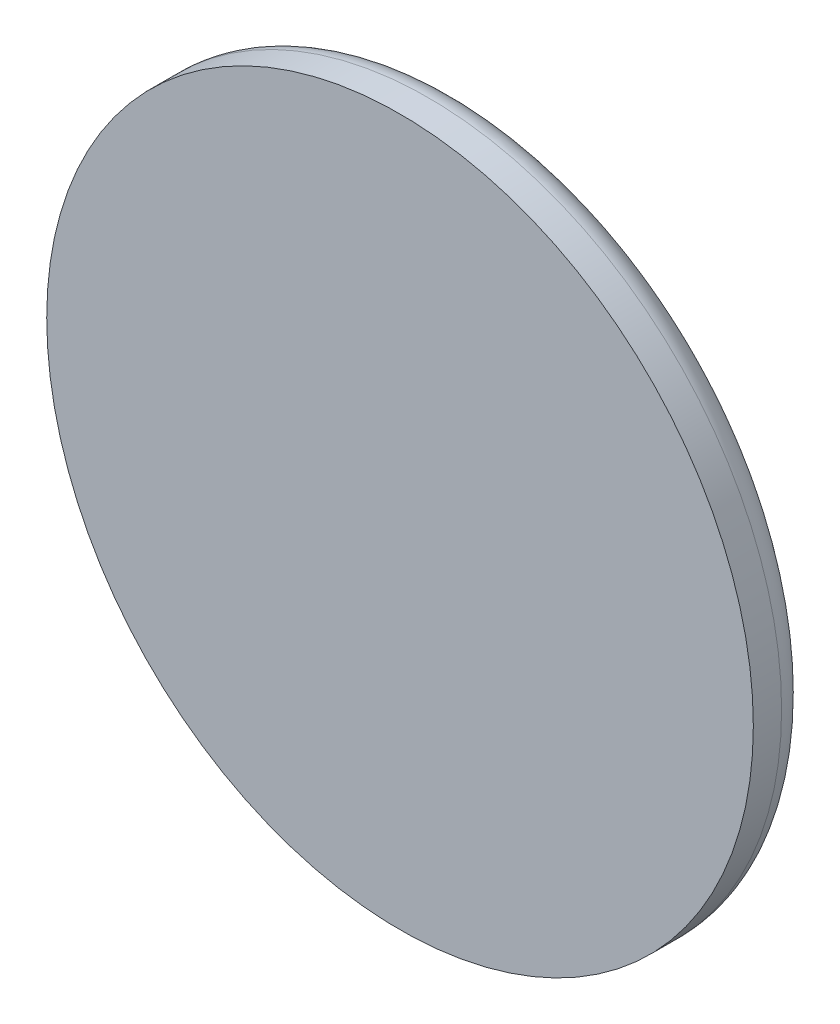
SolidWorks part; units mm, degrees
ref_plane "Front Plane" through (0, 0, 0) normal (0, 0, 1) x (1, 0, 0)
ref_plane "Top Plane" through (0, 0, 0) normal (0, 1, 0) x (1, 0, 0)
ref_plane "Right Plane" through (0, 0, 0) normal (1, 0, 0) x (0, 0, -1)
sketch "Base_Sketch" plane through (0, 0, 0) normal (0, 0, 1) x (1, 0, 0)
  circle A0 centre (0, 0) radius 62.5
  circle A1 centre (0, 0) radius 10
  circle A2 centre (0, 0) radius 5
  dimension "D2" = 10
  dimension "D3" = 125
  dimension "D1" = 5
extrude "Boss-Extrude1" add sketch "Base_Sketch" against normal blind 10 contours A0 A1 | A1 region at (-60.7322, 0, 0)
extrude "Boss-Extrude2" add sketch "Base_Sketch<3>" against normal blind 25 from surface contours A1 A2 region at (-9.7172, 0, 0) starting at face at (62.5, 0, -10)
sketch "Base_Sketch<3>" plane through (0, 0, 0) normal (0, 0, 1) x (1, 0, 0) same geometry as "Base_Sketch"
fillet "Fillet1" radius 5 2 edges at (62.5, 0, -10) (10, 0, -10)
chamfer "Chamfer1" distance 2 angle 45 1 edges at (10, 0, -35)
sketch "Screw_Hole_Ref" plane through (0, 0, -35) normal (0, 0, -1) x (-1, 0, 0)
  line L0 (0, 0) -> (0, 10)
  line L1 (0, 10) -> (-14.3302, 10) construction
  line L2 (0, 0) -> (0, -10)
  line L3 (0, -10) -> (20.6865, -10) construction
  circle A0 centre (0, 0) radius 10 construction
ref_plane "Tangent_Plane" through (0, 10, 0) normal (0, 1, 0) x (1, 0, 0)
sketch "Screw_Hole" plane through (0, 10, 0) normal (0, 1, 0) x (1, 0, 0)
  line L0 (0, 29.6395) -> (0, 12.4581) construction
  point P1 (0, 25)
hole_wizard "CBORE for M2.5 Hex Head Machine Screw1" positions "3DSketch4" profile "Sketch10" counterbore size "M2.5" standard "ANSI Metric" end condition through all
sketch3d "3DSketch4"
  point P0 (0, 10, -25)
sketch "Sketch10" plane through (0, 10, -25) normal (1, 0, 0) x (0, 0, 1)
  line L0 (0, 0) -> (0, 72.5)
  line L1 (0, 72.5) -> (1.55, 72.5)
  line L3 (1.55, 72.5) -> (1.55, 2.1)
  line L4 (1.55, 2.1) -> (3.64, 2.1)
  line L5 (3.64, 2.1) -> (3.64, 0)
  line L7 (3.64, 0) -> (0, 0)
  line L11 (0, -6.35) -> (0, 107.95) construction
  dimension "Thru Hole Dia." = 3.1
  dimension "Thru Hole Depth" = 72.5
  dimension "C'Bore Dia." = 7.28
  dimension "C'Bore Depth" = 2.1
ref_plane "Tangent_Plane_2" through (0, -10, -35) normal (0, -1, 0) x (-1, 0, 0)
sketch "Nut_Extrude" plane through (0, -10, -35) normal (0, -1, 0) x (-1, 0, 0)
  line L1 (2.875, -11.6599) -> (2.875, -8.3401)
  line L2 (2.875, -8.3401) -> (0, -6.6802)
  line L3 (0, -6.6802) -> (-2.875, -8.3401)
  line L4 (-2.875, -8.3401) -> (-2.875, -11.6599)
  line L5 (-2.875, -11.6599) -> (0, -13.3198)
  line L6 (0, -13.3198) -> (2.875, -11.6599)
  circle A0 centre (0, -10) radius 2.875 construction
  point P0 (0, -10)
  dimension "D1" = 5.75
extrude "Cut-Extrude2" cut sketch "Nut_Extrude" against normal blind 2.5 contours L5 L6 L1 L2 L3 L4
equation "\"Base_Radius\"= 125"
equation "\"D3@Base_Sketch\" = \"Base_Radius\""
equation "\"D2@Base_Sketch\" = 10"
equation "\"Screw_Hole_Distance\"= 10mm"
equation "\"D1@Screw_Hole\"=\"Screw_Hole_Distance\""
